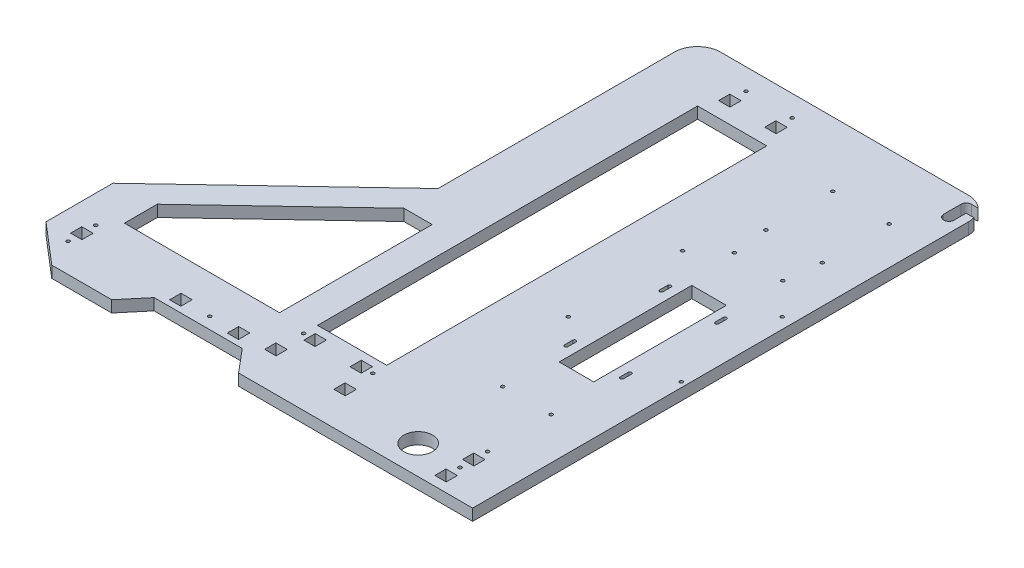
SolidWorks part; units mm, degrees
ref_plane "Front Plane" through (0, 0, 0) normal (0, 0, 1) x (1, 0, 0)
ref_plane "Top Plane" through (0, 0, 0) normal (0, 1, 0) x (1, 0, 0)
ref_plane "Right Plane" through (0, 0, 0) normal (1, 0, 0) x (0, 0, -1)
sketch "Sketch1" plane through (0, 0, 0) normal (0, 1, 0) x (1, 0, 0)
  line L0 (0, 0) -> (-235, 0)
  line L1 (-235, 0) -> (-235, -225)
  line L2 (-235, -225) -> (-380, -362)
  line L3 (-380, -362) -> (-380, -420)
  line L4 (-380, -420) -> (-345, -450)
  line L5 (-345, -450) -> (-293, -450)
  line L6 (-293, -450) -> (-263.6315, -415)
  line L7 (-263.6315, -415) -> (-212.3685, -415)
  line L8 (-212.3685, -415) -> (-183, -450)
  line L9 (-183, -450) -> (0, -450)
  line L10 (0, 0) -> (0, -450)
  line L12 (-293, -450) -> (-183, -450) construction
  dimension "D3" = 235
  dimension "D5" = 58
  dimension "D13" = 190
  dimension "D7" = 35
  dimension "D15" = 52
  dimension "D12" = 30
  dimension "D10" = 35
  dimension "D6" = 380
  dimension "D4" = 450
  dimension "D2" = 50
  dimension "D8" = 50
  dimension "D9" = 110
extrude "Boss-Extrude1" add sketch "Sketch1" along normal blind 10
sketch "Sketch16" plane through (0, 10, 0) normal (0, 1, 0) x (1, 0, 0)
  line L0 (0, -450) -> (20, -450)
  line L1 (20, -450) -> (20, 0)
  line L2 (20, 0) -> (0, 0)
  line L3 (0, 0) -> (0, -450)
  dimension "D1" = 20
  dimension "D2" = 90
extrude "Boss-Extrude2" add sketch "Sketch16" against normal through all
sketch "Sketch2" plane through (0, 10, 0) normal (0, 1, 0) x (1, 0, 0)
  line L0 (-235, -225) -> (-235, -415) construction
  line L1 (-263.6315, -415) -> (-212.3685, -415) construction
  line L2 (-345, -450) -> (-345, -328.931) construction
  line L3 (-235, -225) -> (-380, -362) construction
  line L4 (-345, -358.5097) -> (-235, -254.5787)
  line L5 (-235, -254.5787) -> (-210.5, -254.5787)
  line L6 (-210.5, -254.5787) -> (-210.5, -387)
  line L7 (-210.5, -387) -> (-345, -387)
  line L8 (-345, -387) -> (-345, -358.5097)
  line L9 (0, -450) -> (0, 0) construction
  line L10 (-184.5, -380) -> (-124.5, -380)
  line L11 (-184.5, -380) -> (-184.5, -50.425)
  line L12 (-184.5, -50.425) -> (-124.5, -50.425)
  line L13 (-124.5, -380) -> (-124.5, -50.425)
  line L14 (-124.5, -392.1) -> (-184.5, -392.1) construction
  line L15 (-16, -450) -> (-16, 0) construction
  line L16 (20, 0) -> (-235, 0) construction
  line L17 (-355.9, -440.6571) -> (-355.9, -339.2297) construction
  line L18 (-20.925, -441.85) -> (-11.075, -441.85)
  line L19 (-20.925, -441.85) -> (-20.925, -432.15)
  line L20 (-20.925, -432.15) -> (-11.075, -432.15)
  line L21 (-11.075, -441.85) -> (-11.075, -432.15)
  line L22 (-20.925, -441.85) -> (-11.075, -432.15) construction
  line L23 (-20.925, -432.15) -> (-11.075, -441.85) construction
  line L24 (-20.925, -417.85) -> (-11.075, -417.85)
  line L25 (-20.925, -417.85) -> (-20.925, -408.15)
  line L26 (-20.925, -408.15) -> (-11.075, -408.15)
  line L27 (-11.075, -417.85) -> (-11.075, -408.15)
  line L28 (-20.925, -417.85) -> (-11.075, -408.15) construction
  line L29 (-20.925, -408.15) -> (-11.075, -417.85) construction
  line L30 (-380, -420) -> (-345, -450) construction
  line L32 (-350.975, -408.15) -> (-360.825, -408.15)
  line L33 (-350.975, -408.15) -> (-350.975, -417.85)
  line L34 (-350.975, -417.85) -> (-360.825, -417.85)
  line L35 (-360.825, -408.15) -> (-360.825, -417.85)
  line L36 (-350.975, -408.15) -> (-360.825, -417.85) construction
  line L37 (-350.975, -417.85) -> (-360.825, -408.15) construction
  line L38 (-183, -450) -> (20, -450) construction
  line L39 (-183, -450) -> (20, -450) construction
  line L40 (-173.749, -32.425) -> (-113.749, -32.425) construction
  line L41 (-154.5, -50.425) -> (-154.5, -32.425) construction
  line L42 (-179.425, -27.575) -> (-169.575, -27.575)
  line L43 (-179.425, -27.575) -> (-179.425, -37.275)
  line L44 (-179.425, -37.275) -> (-169.575, -37.275)
  line L45 (-169.575, -27.575) -> (-169.575, -37.275)
  line L46 (-179.425, -27.575) -> (-169.575, -37.275) construction
  line L47 (-179.425, -37.275) -> (-169.575, -27.575) construction
  line L48 (-129.575, -37.275) -> (-139.425, -27.575) construction
  line L49 (-129.575, -27.575) -> (-139.425, -37.275) construction
  line L50 (-139.425, -27.575) -> (-139.425, -37.275)
  line L51 (-129.575, -37.275) -> (-139.425, -37.275)
  line L52 (-129.575, -27.575) -> (-129.575, -37.275)
  line L53 (-129.575, -27.575) -> (-139.425, -27.575)
  line L54 (-174.5, -32.425) -> (-174.5, -18.425) construction
  line L55 (-134.5, -32.425) -> (-134.5, -18.425) construction
  line L56 (-154.5, -380) -> (-154.5, -450) construction
  line L57 (-174.5, -392.1) -> (-134.5, -392.1) construction
  line L58 (-129.65, -397.025) -> (-139.35, -387.175) construction
  line L59 (-179.35, -387.175) -> (-169.65, -387.175)
  line L60 (-179.35, -387.175) -> (-179.35, -397.025)
  line L61 (-179.35, -397.025) -> (-169.65, -397.025)
  line L62 (-169.65, -387.175) -> (-169.65, -397.025)
  line L63 (-179.35, -387.175) -> (-169.65, -397.025) construction
  line L64 (-179.35, -397.025) -> (-169.65, -387.175) construction
  line L65 (-129.65, -387.175) -> (-139.35, -397.025) construction
  line L66 (-139.35, -387.175) -> (-139.35, -397.025)
  line L67 (-129.65, -397.025) -> (-139.35, -397.025)
  line L68 (-129.65, -387.175) -> (-129.65, -397.025)
  line L69 (-129.65, -387.175) -> (-139.35, -387.175)
  line L70 (-119.575, -420.95) -> (-129.425, -411.25) construction
  line L71 (-189.425, -411.25) -> (-179.575, -411.25)
  line L72 (-189.425, -411.25) -> (-189.425, -420.95)
  line L73 (-189.425, -420.95) -> (-179.575, -420.95)
  line L74 (-179.575, -411.25) -> (-179.575, -420.95)
  line L75 (-189.425, -411.25) -> (-179.575, -420.95) construction
  line L76 (-189.425, -420.95) -> (-179.575, -411.25) construction
  line L77 (-119.575, -411.25) -> (-129.425, -420.95) construction
  line L78 (-129.425, -411.25) -> (-129.425, -420.95)
  line L79 (-119.575, -420.95) -> (-129.425, -420.95)
  line L80 (-119.575, -411.25) -> (-119.575, -420.95)
  line L81 (-119.575, -411.25) -> (-129.425, -411.25)
  line L82 (-360.825, -408.15) -> (-11.075, -408.15) construction
  circle A0 centre (-16, -425) radius 1.45
  circle A1 centre (-16, -401) radius 1.45
  circle A2 centre (-355.9, -425) radius 1.45
  circle A3 centre (-355.9, -401) radius 1.45
  circle A4 centre (-174.5, -18.425) radius 1.45
  circle A5 centre (-134.5, -18.425) radius 1.45
  circle A6 centre (-124.5, -392.1) radius 1.45
  circle A7 centre (-184.5, -392.1) radius 1.45
  point P25 (-16, -437)
  point P30 (-16, -413)
  point P44 (-355.9, -413)
  point P61 (-174.5, -32.425)
  point P72 (-134.5, -32.425)
  point P85 (-174.5, -392.1)
  point P94 (-134.5, -392.1)
  point P95 (-184.5, -416.1)
  point P104 (-124.5, -416.1)
  point P105 (-154.5, -392.1)
  dimension "D13" = 2.9
  dimension "D14" = 2.9
  dimension "D23" = 2.9
  dimension "D24" = 2.9
  dimension "D31" = 2.9
  dimension "D37" = 2.9
  dimension "D1" = 21.5
  dimension "D2" = 28
  dimension "D3" = 24.5
  dimension "D4" = 60
  dimension "D7" = 26
  dimension "D8" = 9.7
  dimension "D9" = 9.85
  dimension "D10" = 9.85
  dimension "D11" = 9.7
  dimension "D12" = 24
  dimension "D15" = 24
  dimension "D19" = 9.85
  dimension "D20" = 9.7
  dimension "D26" = 12
  dimension "D27" = 9.85
  dimension "D28" = 9.7
  dimension "D33" = 9.7
  dimension "D38" = 9.85
  dimension "D39" = 9.7
  dimension "D41" = 24
  dimension "D34" = 30
  dimension "D36" = 12.1
  dimension "D30" = 18
  dimension "D29" = 40
  dimension "D17" = 13
  dimension "D32" = 14
  dimension "D35" = 20
  dimension "D16" = 12
  dimension "D21" = 90
  dimension "D25" = 24
  dimension "D5" = 359.75
  dimension "D22" = 349.75
  dimension "D40" = 30
  dimension "D6" = 70
  dimension "D42" = 0
  dimension "D43" = 0
  dimension "D18" = 16
  dimension "D44" = 9.85
extrude "Cut-Extrude1" cut sketch "Sketch2" against normal through all
fillet "Fillet1" radius 20 2 edges at (-235, 5, 0) (20, 5, 0)
sketch "Sketch11" plane through (0, 10, 0) normal (0, 1, 0) x (1, 0, 0)
  line L0 (-124.5, -215.2125) -> (20, -215.2125) construction
  line L1 (20, -450) -> (20, -20) construction
  line L3 (-52.25, -215.2125) -> (-52.25, -450) construction
  line L6 (-124.5, -380) -> (-124.5, -50.425) construction
  line L8 (-183, -450) -> (20, -450) construction
  circle A0 centre (-52.25, -425) radius 12.5
  circle A1 centre (-16, -425) radius 1.45 construction
  dimension "D1" = 25
  dimension "D2" = 0
  dimension "D3" = 0
extrude "WiringHole" cut sketch "Sketch11" against normal through all
sketch "Sketch9" [suppressed] plane through (0, 10, 0) normal (0, 1, 0) x (1, 0, 0)
  line L0 (-52.25, -412.5) -> (-52.25, 0) construction
  line L1 (0, 0) -> (-215, 0) construction
  line L2 (-124.5, -215.2125) -> (20, -215.2125) construction
  line L3 (-124.5, -380) -> (-124.5, -50.425) construction
  line L4 (-27.25, -140.2125) -> (-27.25, -290.2125) construction
  line L6 (-77.25, -140.2125) -> (-27.25, -140.2125) construction
  line L7 (-27.25, -290.2125) -> (-77.25, -290.2125) construction
  line L8 (-77.25, -290.2125) -> (-77.25, -140.2125) construction
  line L9 (20, -450) -> (20, -20) construction
  circle A0 centre (-52.25, -425) radius 12.5 construction
  circle A1 centre (-77.25, -140.2125) radius 1.95
  circle A2 centre (-27.25, -140.2125) radius 1.95
  circle A3 centre (-27.25, -290.2125) radius 1.95
  circle A4 centre (-77.25, -290.2125) radius 1.95
  dimension "D4" = 3.9
  dimension "D1" = 50
  dimension "D2" = 150
  dimension "D5" = 25
extrude "MountingHoles-PSU" [suppressed] cut sketch "Sketch9" against normal through all
sketch "Sketch10" plane through (0, 10, 0) normal (0, 1, 0) x (1, 0, 0)
  line L0 (-124.5, -215.2125) -> (20, -215.2125) construction
  line L1 (20, -450) -> (20, -20) construction
  line L2 (-52.25, -245.2125) -> (-22.25, -245.2125) construction
  line L3 (-37.25, -210.225) -> (-37.25, 0) construction
  line L4 (-52.25, -215.2125) -> (-52.25, -184.5972) construction
  line L7 (-124.5, -380) -> (-124.5, -50.425) construction
  line L8 (-52.25, -302.7125) -> (-22.25, -302.7125)
  line L9 (-52.25, -302.7125) -> (-52.25, -187.7125)
  line L10 (-52.25, -187.7125) -> (-22.25, -187.7125)
  line L11 (-22.25, -302.7125) -> (-22.25, -187.7125)
  line L12 (-52.25, -302.7125) -> (-22.25, -187.7125) construction
  line L13 (-52.25, -187.7125) -> (-22.25, -302.7125) construction
  line L15 (0, 0) -> (-215, 0) construction
  line L17 (-37.25, -210.225) -> (-37.25, -450) construction
  line L18 (-183, -450) -> (20, -450) construction
  line L19 (-64.75, -215.2125) -> (-39.75, -215.2125) construction
  line L20 (-37.25, -302.7125) -> (-37.25, -187.7125) construction
  dimension "D1" = 30
  dimension "D2" = 115
  dimension "D3" = 0
  dimension "D4" = 0
  dimension "D5" = 0
  dimension "D6" = 30
  dimension "D7" = 15
extrude "WiringSlot" cut sketch "Sketch10" against normal through all
sketch "CenterLines" plane through (0, 10, 0) normal (0, 1, 0) x (1, 0, 0)
  line L0 (-37.25, -302.7125) -> (-37.25, -187.7125) construction
  line L1 (-52.25, -302.7125) -> (-22.25, -302.7125) construction
  line L2 (-22.25, -187.7125) -> (-52.25, -187.7125) construction
  line L3 (-52.25, -245.2125) -> (-22.25, -245.2125) construction
  line L4 (-52.25, -187.7125) -> (-52.25, -302.7125) construction
  line L5 (-22.25, -302.7125) -> (-22.25, -187.7125) construction
ref_plane "Plane1" through (-37.25, 0, 0) normal (1, 0, 0) x (0, 0, -1)
sketch "Sketch6" plane through (0, 10, 0) normal (0, 1, 0) x (1, 0, 0)
  line L0 (-37.25, -302.7125) -> (-37.25, -187.7125) construction
  line L1 (-61.35, -242.7125) -> (-13.15, -242.7125) construction
  line L2 (-13.15, -197.9625) -> (-13.15, -280.4625) construction
  line L3 (-52.25, -302.7125) -> (-22.25, -302.7125) construction
  line L4 (-52.25, -240.2125) -> (-22.25, -240.2125) construction
  line L5 (-22.25, -187.7125) -> (-52.25, -187.7125) construction
  line L6 (-13.15, -197.9625) -> (-13.15, -204.9625) construction
  line L7 (-11.7, -197.9625) -> (-11.7, -204.9625)
  line L8 (-14.6, -197.9625) -> (-14.6, -204.9625)
  line L9 (-52.25, -245.2125) -> (-22.25, -245.2125) construction
  line L10 (-52.25, -187.7125) -> (-52.25, -302.7125) construction
  line L11 (-22.25, -302.7125) -> (-22.25, -187.7125) construction
  line L12 (-13.15, -287.4625) -> (-13.15, -280.4625) construction
  line L13 (-14.6, -287.4625) -> (-14.6, -280.4625)
  line L14 (-61.35, -280.4625) -> (-61.35, -204.9625) construction
  line L15 (-13.15, -287.4625) -> (-13.15, -204.9625) construction
  line L16 (-11.7, -287.4625) -> (-11.7, -280.4625)
  arc A2 (-11.7, -197.9625) -> (-14.6, -197.9625) centre (-13.15, -197.9625) ccw
  arc A3 (-14.6, -204.9625) -> (-11.7, -204.9625) centre (-13.15, -204.9625) ccw
  circle A4 centre (-61.35, -280.4625) radius 1.45
  circle A6 centre (-61.35, -204.9625) radius 1.45
  arc A8 (-14.6, -287.4625) -> (-11.7, -287.4625) centre (-13.15, -287.4625) ccw
  arc A9 (-11.7, -280.4625) -> (-14.6, -280.4625) centre (-13.15, -280.4625) ccw
  point P20 (-13.15, -201.4625)
  point P25 (-13.15, -283.9625)
  dimension "D8" = 2.9
  dimension "D12" = 2.9
  dimension "D4" = 1.45
  dimension "D5" = 1.45
  dimension "D11" = 82.5
  dimension "D14" = 75.5
  dimension "D2" = 24.1
  dimension "D3" = 48.2
  dimension "D6" = 2.5
  dimension "D9" = 7
  dimension "D10" = 7
extrude "MountingHoles-RAMPS" cut sketch "Sketch6" against normal through all
mirror "Mirror1" about plane through (-37.25, 0, 0) normal (1, 0, 0) of "MountingHoles-RAMPS"
sketch "Sketch5" plane through (0, 10, 0) normal (0, 1, 0) x (1, 0, 0)
  line L0 (-22.25, -245.2125) -> (-52.25, -245.2125) construction
  line L3 (-22.25, -302.7125) -> (-22.25, -187.7125) construction
  line L5 (-52.25, -187.7125) -> (-52.25, -302.7125) construction
  line L7 (-16.25, -144.7125) -> (-58.25, -144.7125) construction
  line L8 (-16.25, -345.7125) -> (-58.25, -345.7125) construction
  line L9 (-37.25, -245.2125) -> (-37.25, -144.7125) construction
  line L10 (-37.25, -245.2125) -> (-37.25, -345.7125) construction
  circle A0 centre (-58.25, -144.7125) radius 1.45
  circle A1 centre (-16.25, -144.7125) radius 1.45
  circle A2 centre (-16.25, -345.7125) radius 1.45
  circle A3 centre (-58.25, -345.7125) radius 1.45
  point P17 (-37.25, -144.7125)
  point P22 (-37.25, -345.7125)
  dimension "D2" = 2.9
  dimension "D5" = 2.9
  dimension "D6" = 2.9
  dimension "D7" = 2.9
  dimension "D3" = 201
  dimension "D4" = 100.5
  dimension "D8" = 21
  dimension "D9" = 21
  dimension "D10" = 100.5
extrude "MountingHoles-Melzi" cut sketch "Sketch5" against normal through all
sketch "Sketch13" plane through (0, 0, 0) normal (0, -1, 0) x (-1, 0, 0)
  line L0 (52.25, -215.2125) -> (124.5, -215.2125) construction
  line L1 (124.5, -380) -> (124.5, -50.425) construction
  line L2 (82.25, -264.7275) -> (82.25, -165.6975) construction
  line L3 (37.25, -302.7125) -> (37.25, -187.7125) construction
  line L4 (52.25, -187.7125) -> (52.25, -302.7125) construction
  line L6 (82.25, -264.7275) -> (-15.65, -264.7275) construction
  circle A0 centre (82.25, -165.6975) radius 1.45
  circle A1 centre (82.25, -264.7275) radius 1.45
  circle A2 centre (-10.59, -172.1775) radius 1.45
  circle A3 centre (-15.65, -264.7275) radius 1.45
  point P11 (82.25, -215.2125)
  dimension "D8" = 2.9
  dimension "D6" = 2.9
  dimension "D1" = 2.9
  dimension "D2" = 49.515
  dimension "D3" = 45
  dimension "D4" = 6.48
  dimension "D5" = 92.84
  dimension "D7" = 97.9
extrude "Mountingholes-Smoothieboard" cut sketch "Sketch13" against normal through all
mirror "Flipped" [suppressed] about plane through (-37.25, 0, 0) normal (1, 0, 0)
sketch "Sketch21" plane through (0, 10, 0) normal (0, 1, 0) x (1, 0, 0)
  line L0 (-37.25, -187.7125) -> (-37.25, 0) construction
  line L1 (-22.25, -187.7125) -> (-52.25, -187.7125) construction
  line L2 (0, 0) -> (-215, 0) construction
  line L3 (-37.25, -85) -> (-23.3697, -85) construction
  circle A0 centre (-12.75, -56) radius 1.45
  circle A1 centre (-61.75, -56) radius 1.45
  circle A2 centre (-61.75, -114) radius 1.45
  circle A3 centre (-12.75, -114) radius 1.45
  dimension "D1" = 2.9
  dimension "D2" = 24.5
  dimension "D3" = 29
  dimension "D4" = 85
extrude "Pi" cut sketch "Sketch21" against normal through all
sketch "Sketch17" plane through (0, 10, 0) normal (0, 1, 0) x (1, 0, 0)
  line L0 (0, 0) -> (20, 0) construction
  line L1 (20, -23.6361) -> (20, 0) construction
  line L2 (20, -450) -> (20, -20) construction
  line L3 (20, -10) -> (8, -10) construction
  line L4 (20, -14.5) -> (8, -14.5)
  line L5 (20, -5.5) -> (8, -5.5)
  arc A0 (20, -14.5) -> (20, -5.5) centre (20, -10) ccw
  arc A1 (8, -5.5) -> (8, -14.5) centre (8, -10) ccw
  point P8 (14, -10)
  dimension "D1" = 9
  dimension "D2" = 12
  dimension "D3" = 10
extrude "Cut-Extrude3" cut sketch "Sketch17" against normal through all
sketch "Sketch18" plane through (0, 10, 0) normal (0, 1, 0) x (1, 0, 0)
  line L0 (8, -5.5) -> (8, -14.5) construction
  line L1 (3.5, -10) -> (8, -10) construction
  line L2 (8, -10) -> (8, -25) construction
  line L3 (12.5, -10) -> (12.5, -25)
  line L4 (3.5, -10) -> (3.5, -25)
  arc A0 (8, -5.5) -> (8, -14.5) centre (8, -10) ccw construction
  arc A1 (12.5, -10) -> (3.5, -10) centre (8, -10) ccw
  arc A2 (3.5, -25) -> (12.5, -25) centre (8, -25) ccw
  point P10 (8, -17.5)
  dimension "D1" = 9
  dimension "D2" = 0
  dimension "D3" = 15
extrude "Cut-Extrude4" cut sketch "Sketch18" against normal through all
sketch "Sketch19" plane through (0, 10, 0) normal (0, 1, 0) x (1, 0, 0)
  line L0 (-2, -25) -> (18, -25) construction
  line L1 (8, -25) -> (8, -5.5) construction
  circle A0 centre (18, -25) radius 1.45
  arc A1 (8, -5.5) -> (3.5, -10) centre (8, -10) ccw construction
  circle A2 centre (-2, -25) radius 1.45
  dimension "D2" = 2.9
extrude "Cut-Extrude5" [suppressed] cut sketch "Sketch19" against normal through all
sketch "Sketch22" plane through (0, 10, 0) normal (0, 1, 0) x (1, 0, 0)
  line L0 (-276.218, -430) -> (-199.782, -430)
  line L1 (-293, -450) -> (-263.6315, -415) construction
  line L2 (-212.3685, -415) -> (-183, -450) construction
  line L3 (-199.782, -430) -> (-212.3685, -415)
  line L4 (-212.3685, -415) -> (-263.6315, -415)
  line L5 (-263.6315, -415) -> (-276.218, -430)
  dimension "D1" = 15
extrude "Boss-Extrude3" add sketch "Sketch22" against normal through all
sketch "Sketch23" plane through (0, 10, 0) normal (0, 1, 0) x (1, 0, 0)
  line L0 (-238, -430) -> (-238, -387) construction
  line L1 (-276.218, -430) -> (-199.782, -430) construction
  line L2 (-345, -387) -> (-210.5, -387) construction
  line L3 (-213, -420) -> (-263, -420) construction
  line L4 (-179.35, -387.175) -> (-179.35, -397.025) construction
  line L5 (-267.85, -415.075) -> (-258.15, -415.075)
  line L6 (-267.85, -415.075) -> (-267.85, -424.925)
  line L7 (-267.85, -424.925) -> (-258.15, -424.925)
  line L8 (-258.15, -415.075) -> (-258.15, -424.925)
  line L9 (-267.85, -415.075) -> (-258.15, -424.925) construction
  line L10 (-267.85, -424.925) -> (-258.15, -415.075) construction
  line L11 (-208.15, -424.925) -> (-217.85, -415.075) construction
  line L12 (-208.15, -415.075) -> (-217.85, -424.925) construction
  line L13 (-217.85, -415.075) -> (-217.85, -424.925)
  line L14 (-208.15, -424.925) -> (-217.85, -424.925)
  line L15 (-208.15, -415.075) -> (-208.15, -424.925)
  line L16 (-208.15, -415.075) -> (-217.85, -415.075)
  circle A0 centre (-238, -420) radius 1.45
  point P19 (-238, -420)
  dimension "D4" = 2.9
  dimension "D1" = 9.7
  dimension "D3" = 10
extrude "Cut-Extrude6" cut sketch "Sketch23" against normal through all
equation "\"Y-ROD-SPACING\"=75"
equation "\"Y-BED-OFFSET\"=2"
equation "\"Y-BED-ROD-INSET\"=3.5"
equation "\"T-SLOT-NUT-FILLET-RADIUS\"=0.5"
equation "\"T-SLOT-SCREW-SHAFT-RADIUS\"=1.55"
equation "\"T-SLOT-SCREW-SHAFT-CUTOUT-LENGTH\"=11"
equation "\"T-SLOT-NUT-DEPTH\"=3.5"
equation "\"T-SLOT-NUT-WIDTH\"=2.85"
equation "\"T-SLOT-NUT-END-DISTANCE\"=8"
equation "\"ACRYLIC-TAB-CUTOUT-SIZE\"=\"ACRYLIC-THICKNESS\"+\"ACRYLIC-TAB-TOLERANCE\"*2"
equation "\"ACRYLIC-TAB-WIDTH\"=\"ACRYLIC-THICKNESS\""
equation "\"ACRYLIC-M3-HOLE\"=2.9"
equation "\"SMOOTHROD-CAP-SCREW-DISTANCE\"=20"
equation "\"FRAME-WIDTH-INNER\"=370"
equation "\"D24@Sketch2\"=\"ACRYLIC-M3-HOLE\""
equation "\"D23@Sketch2\"=\"ACRYLIC-M3-HOLE\""
equation "\"D19@Sketch2\"=\"ACRYLIC-THICKNESS\"-\"KERF\"*2"
equation "\"D20@Sketch2\"=\"ACRYLIC-TAB-WIDTH\"-\"KERF\"*4"
equation "\"D37@Sketch2\"=\"ACRYLIC-M3-HOLE\""
equation "\"D33@Sketch2\"=\"ACRYLIC-TAB-WIDTH\"-\"KERF\"*4"
equation "\"D38@Sketch2\"=\"ACRYLIC-THICKNESS\"-\"KERF\"*2"
equation "\"D39@Sketch2\"=\"ACRYLIC-TAB-WIDTH\"-\"KERF\"*4"
equation "\"D13@Sketch2\"=\"ACRYLIC-M3-HOLE\""
equation "\"D14@Sketch2\"=\"ACRYLIC-M3-HOLE\""
equation "\"D8@Sketch2\"=\"ACRYLIC-TAB-WIDTH\"-\"KERF\"*4"
equation "\"D9@Sketch2\"=\"ACRYLIC-THICKNESS\"-\"KERF\"*2"
equation "\"D10@Sketch2\"=\"ACRYLIC-THICKNESS\"-\"KERF\"*2"
equation "\"D11@Sketch2\"=\"ACRYLIC-TAB-WIDTH\"-\"KERF\"*4"
equation "\"D31@Sketch2\"=\"ACRYLIC-M3-HOLE\""
equation "\"D27@Sketch2\"=\"ACRYLIC-THICKNESS\"-\"KERF\"*2"
equation "\"D28@Sketch2\"=\"ACRYLIC-TAB-WIDTH\"-\"KERF\"*4"
equation "\"NEMA17-HOLE-SPACING\"=31"
equation "\"NEMA17-CENTRAL-CUTOUT\"=22.5"
equation "\"Z-BRACKET-REACH\"=57"
equation "\"TOP-BRACKET-SPACING\"=40"
equation "\"D29@Sketch2\"=\"TOP-BRACKET-SPACING\""
equation "\"ACRYLIC-THICKNESS\"=10"
equation "\"SMOOTHROD-Z-LENGTH\"=350"
equation "\"D5@Sketch2\"=\"SMOOTHROD-Z-LENGTH\"-\"SMOOTHROD-TIGHTENING-HEADROOM\"+10"
equation "\"SMOOTHROD-X-LENGTH\"=350"
equation "\"SMOOTHROD-Y-LENGTH\"=350"
equation "\"D22@Sketch2\"=\"SMOOTHROD-Y-LENGTH\"-\"SMOOTHROD-TIGHTENING-HEADROOM\""
equation "\"SMOOTHROD-TIGHTENING-HEADROOM\"=.25"
equation "\"X-ROD-SPACING\"=45"
equation "\"Z-ROD-SPACING\"=17.5"
equation "\"LEADSCREW-Z-LENGTH\"=300"
equation "\"SCREW-HEAD-RADIUS\"=6"
equation "\"PRINTED-X-SMOOTHROD-DIAMETER\"=8.8"
equation "\"PRINTED-X-SMOOTHROD-CUTOUT\"=10"
equation "\"PRINTED-X-BASE-HEIGHT\"=10"
equation "\"PRINTED-LM8UU-CUTOUT-SIZE\"=15.5"
equation "\"PRINTED-LM8UU-CUTOUT-LENGTH\"=24.5"
equation "\"PRINTED-X-IDLER-HEIGHT\"=16"
equation "\"PSU-MOUNTING-WIDTH\"=50"
equation "\"PSU-MOUNTING-HEIGHT\"=150"
equation "\"D1@Sketch9\"=\"PSU-MOUNTING-WIDTH\""
equation "\"D1@Boss-Extrude1\"=\"ACRYLIC-THICKNESS\""
equation "\"D6@Sketch1\"=\"SMOOTHROD-Y-LENGTH\"+30"
equation "\"D4@Sketch9\"=\"ACRYLIC-M4-HOLE\""
equation "\"D2@Sketch9\"=\"PSU-MOUNTING-HEIGHT\""
equation "\"D5@Sketch9\"=\"PSU-MOUNTING-WIDTH\"/2"
equation "\"D4@Sketch1\"=\"SMOOTHROD-Z-LENGTH\"+100"
equation "\"D8@Sketch6\"=\"ACRYLIC-M3-HOLE\""
equation "\"D12@Sketch6\"=\"ACRYLIC-M3-HOLE\""
equation "\"D2@Sketch5\"=\"ACRYLIC-M3-HOLE\""
equation "\"D5@Sketch5\"=\"ACRYLIC-M3-HOLE\""
equation "\"D6@Sketch5\"=\"ACRYLIC-M3-HOLE\""
equation "\"D7@Sketch5\"=\"ACRYLIC-M3-HOLE\""
equation "\"D1@Sketch13\"=\"ACRYLIC-M3-HOLE\""
equation "\"D6@Sketch13\"=\"ACRYLIC-M3-HOLE\""
equation "\"D8@Sketch13\"=\"ACRYLIC-M3-HOLE\""
equation "\"D4@Sketch6\"=\"ACRYLIC-M3-HOLE\"/2"
equation "\"D5@Sketch6\"=\"ACRYLIC-M3-HOLE\"/2"
equation "\"Y-BED-SCREW-SPACING\"=209"
equation "\"Y-BED-SCREW-CUTOUT-SLOT-HEIGHT\"=2.5"
equation "\"ACRYLIC-THICKNESS2\"=4.5"
equation "\"ACRYLIC-TAB-TOLERANCE\"=-.05"
equation "\"Z-ROD-INSET\"=13.5"
equation "\"SCREW-LENGTH-FRAME\"=\"ACRYLIC-THICKNESS\" + 10"
equation "\"SCREW-LENGTH-MOTOR\"=\"ACRYLIC-THICKNESS\" + 5"
equation "\"SCREW-LENGTH-EXTRUDER\"=28"
equation "\"Y-BELT-TO-ROD-DISTANCE\"=20"
equation "\"SPOOL-HOLDER-ROD-SPACING\"=150"
equation "\"ACRYLIC-X-CARRIAGE-WIDTH\"=55"
equation "\"ACRYLIC-X-CARRIAGE-HEIGHT\"=75"
equation "\"ACRYLIC-X-CARRIAGE-LM8UU-CUTOUT-WIDTH\"=24.25"
equation "\"ACRYLIC-X-CARRIAGE-SCREW-SPACING-X\"=15"
equation "\"ACRYLIC-X-CARRIAGE-SCREW-SPACING-Y\"=33"
equation "\"ACRYLIC-X-CARRIAGE-CENTER-TAB-SPACING\"=14"
equation "\"ACRYLIC-X-CARRIAGE-EXTRUDER-OFFSET\"=26"
equation "\"ACRYLIC-X-CARRIAGE-EXTRUDER-ANGLE\"=90"
equation "\"ACRYLIC-X-CARRIAGE-EXTRUDER-SHELF-DEPTH\"=\"ACRYLIC-X-CARRIAGE-EXTRUDER-OFFSET\" + 28"
equation "\"ACRYLIC-X-CARRIAGE-EXTRUDER-BRACE-SPACING\"=23"
equation "\"ACRYLIC-X-CARRIAGE-EXTRUDER-BRACE-TAB-OFFSET\"=20"
equation "\"ACRYLIC-X-CARRIAGE-EXTRUDER-BRACE-HEIGHT\"=35"
equation "\"ACRYLIC-X-CARRIAGE-EXTRUDER-BRACE-SCREW-SPACING\"=22"
equation "\"D1@Sketch19\"=\"SMOOTHROD-CAP-SCREW-DISTANCE\"/2"
equation "\"D2@Sketch19\"=\"ACRYLIC-M3-HOLE\""
equation "\"D1@Sketch21\"=\"ACRYLIC-M3-HOLE\""
equation "\"KERF\"=0.075"
equation "\"PRINTED-M3-HOLE\"=3.5"
equation "\"PRINTED-M3-NUT-AF\"=6.25"
equation "\"ACRYLIC-X-CARRIAGE-LM8UU-CUTOUT-HEIGHT\"=11.0"
equation "\"ACRYLIC-X-CARRIAGE-DUAL-WIDTH-MULTIPLIER\"=1.65"
equation "\"ACRYLIC-X-CARRIAGE-DUAL-HOTEND-SPACING\"=42"
equation "\"ACRYLIC-X-CARRIAGE-DUAL-WIDTH\"=75"
equation "\"ACRYLIC-X-CARRIAGE-DUAL-FAN-OFFSET\"=52"
equation "\"ACRYLIC-X-CARRIAGE-DUAL-FAN-HEIGHT\"=20"
equation "\"ACRYLIC-X-CARRIAGE-DUAL-HOTEND-SEPARATION\"=36"
equation "\"ACRYLIC-X-CARRIAGE-DUAL-MOUNT-PLATE-DEPTH\"=75"
equation "\"ACRYLIC-X-CARRIAGE-DUAL-MOUNT-BRACE-WIDTH\"=33"
equation "\"ACRYLIC-X-CARRIAGE-DUAL-MOUNT-SCREW-WIDTH\"=40"
equation "\"BLOWER-FAN-WIDTH\"=15"
equation "\"D44@Sketch2\"=\"ACRYLIC-THICKNESS\"-\"KERF\"*2"
equation "\"D1@Sketch23\"=10-\"KERF\"*4"
equation "\"D4@Sketch23\"=\"ACRYLIC-M3-HOLE\""
equation "\"ACRYLIC-THICKNESS-TAB-CUTOUT-WIDTH\"=\"ACRYLIC-THICKNESS\"-\"KERF\"*2"
equation "\"ACRYLIC-THICKNESS-TAB-CUTOUT-HEIGHT\"=\"ACRYLIC-TAB-WIDTH\"-\"KERF\"*4"
equation "\"ACRYLIC-THICKNESS2-TAB-CUTOUT-WIDTH\"=\"ACRYLIC-THICKNESS2\"-\"KERF\"*2"
equation "\"ACRYLIC-THICKNESS2-TAB-CUTOUT-HEIGHT\"=\"ACRYLIC-TAB-WIDTH\"-\"KERF\"*4"
equation "\"ACRYLIC-M4-HOLE\"=3.9"
